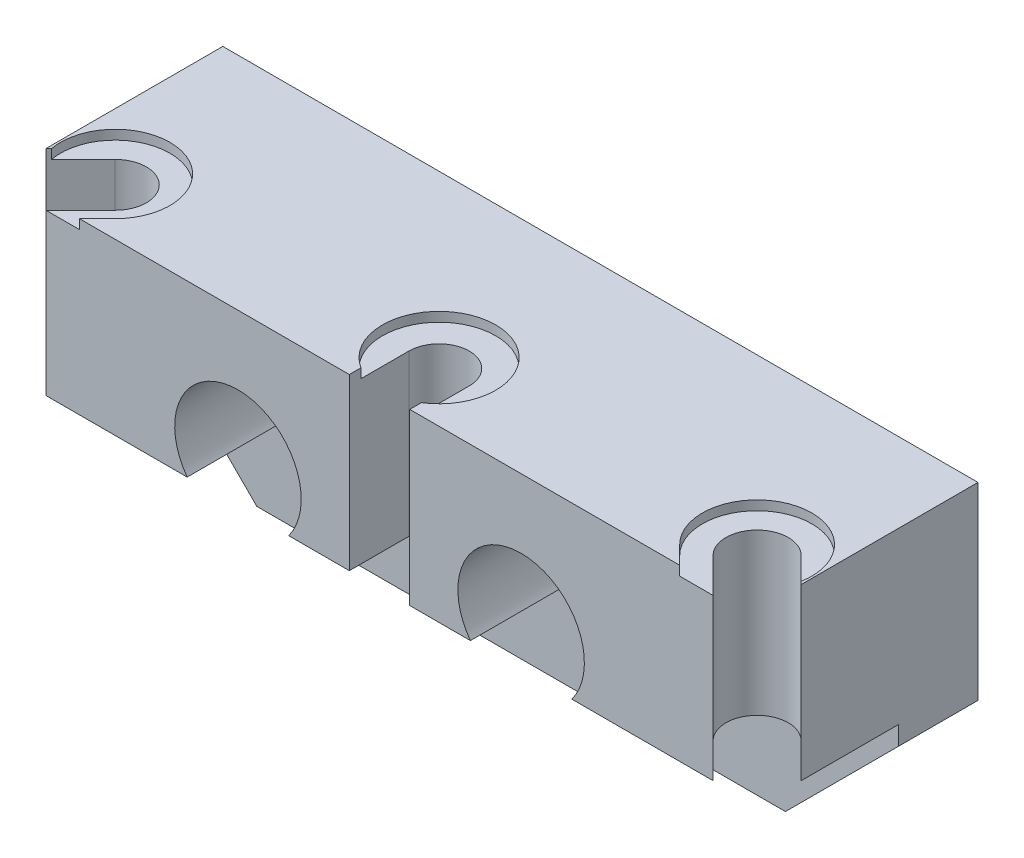
SolidWorks part; units mm, degrees
ref_plane "Front Plane" through (0, 0, 0) normal (0, 0, 1) x (1, 0, 0)
ref_plane "Top Plane" through (0, 0, 0) normal (0, 1, 0) x (1, 0, 0)
ref_plane "Right Plane" through (0, 0, 0) normal (1, 0, 0) x (0, 0, -1)
sketch "Sketch1" plane through (0, 0, 0) normal (0, 0, 1) x (1, 0, 0)
  line L1 (-20, 0) -> (20, 0)
  line L2 (-20, 0) -> (-20, 16)
  line L3 (-20, 16) -> (20, 16)
  line L4 (20, 0) -> (20, 16)
  dimension "D2" = 40
  dimension "D3" = 16
extrude "Boss-Extrude1" add sketch "Sketch1" along normal blind 12
sketch "Sketch2" plane through (0, 0, 12) normal (0, 0, 1) x (1, 0, 0)
  line L0 (0, 8) -> (0, 9) construction
  line L2 (-7.5, 9) -> (7.5, 9) construction
  line L3 (20, 16) -> (-20, 16) construction
  line L4 (-7.5, 5) -> (-7.5, 13) construction
  line L5 (-9.15, 5) -> (-9.15, 13) construction
  line L6 (-5.85, 5) -> (-5.85, 13) construction
  line L7 (7.5, 5) -> (7.5, 13) construction
  line L8 (5.85, 5) -> (5.85, 13) construction
  line L9 (9.15, 5) -> (9.15, 13) construction
  line L10 (-16, 8) -> (16, 8) construction
  arc A0 (-9.15, 5) -> (-5.85, 5) centre (-7.5, 5) ccw construction
  arc A1 (-5.85, 13) -> (-9.15, 13) centre (-7.5, 13) ccw construction
  arc A2 (5.85, 5) -> (9.15, 5) centre (7.5, 5) ccw construction
  arc A3 (9.15, 13) -> (5.85, 13) centre (7.5, 13) ccw construction
  circle A4 centre (-16, 8) radius 1.7784 construction
  circle A5 centre (16, 8) radius 1.7784 construction
  circle A6 centre (-7.5, 9) radius 1.65
  circle A7 centre (7.5, 9) radius 1.65
  point P8 (-7.5, 9)
  point P15 (7.5, 9)
  dimension "D1" = 1.65
  dimension "D2" = 8
  dimension "D3" = 7
  dimension "D4" = 15
  dimension "D5" = 1
  dimension "D6" = 32
extrude "Cut-Extrude1" cut sketch "Sketch2" against normal through all
sketch "Sketch5" plane through (0, 16, 0) normal (0, 1, 0) x (1, 0, 0)
  line L0 (0, 0) -> (0, -9) construction
  line L1 (-17, -9) -> (17, -9) construction
  line L2 (20, -12) -> (-20, -12) construction
  line L3 (-18.1667, -7.8333) -> (-20, -9.6665)
  line L4 (-20, -9.6665) -> (-17.6665, -12) construction
  line L5 (-17.6665, -12) -> (-15.8333, -10.1667)
  line L6 (-20, -9.6665) -> (-20, -12)
  line L7 (-20, -12) -> (-17.6665, -12)
  line L8 (15.8333, -10.1667) -> (17.6665, -12)
  line L9 (-20, -12) -> (-20, 0) construction
  line L10 (17.6665, -12) -> (20, -12)
  line L11 (20, -12) -> (20, -9.6665)
  line L12 (20, -12) -> (20, 0) construction
  line L13 (20, -9.6665) -> (18.1667, -7.8333)
  arc A0 (-15.8333, -10.1667) -> (-18.1667, -7.8333) centre (-17, -9) ccw
  arc A1 (18.1667, -7.8333) -> (15.8333, -10.1667) centre (17, -9) ccw
  dimension "D2" = 3.3
  dimension "D1" = 45
  dimension "D3" = 3
extrude "Cut-Extrude4" cut sketch "Sketch5" against normal through all
sketch "Sketch6" plane through (20, 0, 0) normal (1, 0, 0) x (0, 0, -1)
  line L0 (-12, 7) -> (-4.5, 7)
  line L3 (-4.5, 7) -> (-4.5, 0)
  line L4 (-9.6665, 0) -> (0, 0) construction
  line L5 (-4.5, 0) -> (-12, 0)
  line L6 (-12, 0) -> (-12, 7)
  line L8 (-9.6665, 16) -> (0, 16) construction
  line L9 (0, 0) -> (0, 16) construction
  dimension "D1" = 9
  dimension "D2" = 4.5
extrude "Cut-Extrude5" cut sketch "Sketch6" against normal through all
sketch "Sketch7" plane through (0, 16, 0) normal (0, 1, 0) x (1, 0, 0)
  line L1 (-19.0506, -11.0506) -> (-17, -13.1012)
  line L2 (-17, -13.1012) -> (-14.9494, -11.0506)
  line L3 (0, 0) -> (0, -12) construction
  line L4 (20, 0) -> (-20, 0) construction
  line L6 (17, -13.1012) -> (14.9494, -11.0506)
  line L7 (19.0506, -11.0506) -> (17, -13.1012)
  arc A0 (-14.9494, -11.0506) -> (-19.0506, -11.0506) centre (-17, -9) ccw
  arc A1 (14.9494, -11.0506) -> (19.0506, -11.0506) centre (17, -9) cw
  dimension "D1" = 5.8
extrude "Cut-Extrude6" cut sketch "Sketch7" against normal blind 0.5
chamfer "Chamfer4" [suppressed] distance 1.8 angle 45
sketch "Sketch8" plane through (0, 16, 0) normal (0, 1, 0) x (1, 0, 0)
  line L0 (-1.6, -8.8461) -> (-1.6, -12)
  line L1 (15.8988, -12) -> (-15.8988, -12) construction
  line L2 (-1.6, -12) -> (1.6, -12)
  line L3 (1.6, -12) -> (1.6, -8.8461)
  arc A0 (1.6, -9.0461) -> (-1.6, -9.0461) centre (0, -9.0461) ccw construction
  arc A1 (1.6, -8.8461) -> (-1.6, -8.8461) centre (0, -8.8461) ccw
  dimension "D1" = 1.6
  dimension "D2" = 0.2
extrude "Cut-Extrude7" cut sketch "Sketch8" against normal through all
sketch "Sketch9" plane through (0, 0, 12) normal (0, 0, 1) x (1, 0, 0)
  circle A0 centre (-7.5, 9) radius 3.35
  circle A1 centre (7.5, 9) radius 3.35
  dimension "D1" = 6.7
extrude "Cut-Extrude8" cut sketch "Sketch9" against normal up to surface (7.5 mm away) up to face at (0, 3.5, 4.5)
chamfer "Chamfer5" distance 1.8 angle 45 2 edges at (-7.5, 10.65, 4.5) (7.5, 10.65, 4.5)
chamfer "Chamfer6" distance 6 angle 45 2 edges at (20, 0, 2.25) (-20, 0, 2.25)
chamfer "Chamfer7" distance 0.3 angle 45 8 edges at (0, 16, 0) (-20, 11, 0) (-17, 3, 0) (0, 0, 0) (17, 3, 0) (20, 11, 0) (-5.85, 9, 0) (9.15, 9, 0)
sketch "Sketch10" plane through (0, 15.5, 0) normal (0, 1, 0) x (1, 0, 0)
  circle A0 centre (17, -9) radius 2.9
  circle A1 centre (-17, -9) radius 2.9
  arc A4 (-14.9494, -11.0506) -> (-19.8531, -9.5196) centre (-17, -9) ccw construction
  arc A5 (19.8531, -9.5196) -> (14.9494, -11.0506) centre (17, -9) ccw construction
  dimension "D1" = 5.8
extrude "Cut-Extrude9" [suppressed] cut sketch "Sketch10" against normal blind 0.5
sketch "Sketch11" plane through (0, 16, 0) normal (0, 1, 0) x (1, 0, 0)
  circle A0 centre (0, -8.8461) radius 3
  arc A1 (1.6, -8.8461) -> (-1.6, -8.8461) centre (0, -8.8461) ccw construction
  dimension "D1" = 6
extrude "Cut-Extrude10" cut sketch "Sketch11" against normal up to surface (0.5 mm away) up to face at (16.6559, 15.5, 9.5584)
equation "\"y-cross-rib-thickness\"=6"
equation "\"y-rib-thickness\"=6"
equation "\"bed-plate-thickness\"=6"
equation "\"x-plate-thickness\"=5"
equation "\"rod-diameter\"=12"
equation "\"t-nut-hole-diameter\"=3"
equation "\"y-plate-thickness\"=5"
equation "\"enclosure-thickness\"=0.6"
equation "\"M3-Clearance\"=3.3"
equation "\"M4-Clearance\"=4.3"
equation "\"M5-Clearance\"=5.3"
equation "\"M6-Clearance\"=6.3"
equation "\"M8-Clearance\"=8.3"
equation "\"623-Bearing-Dia\"=11.2"
